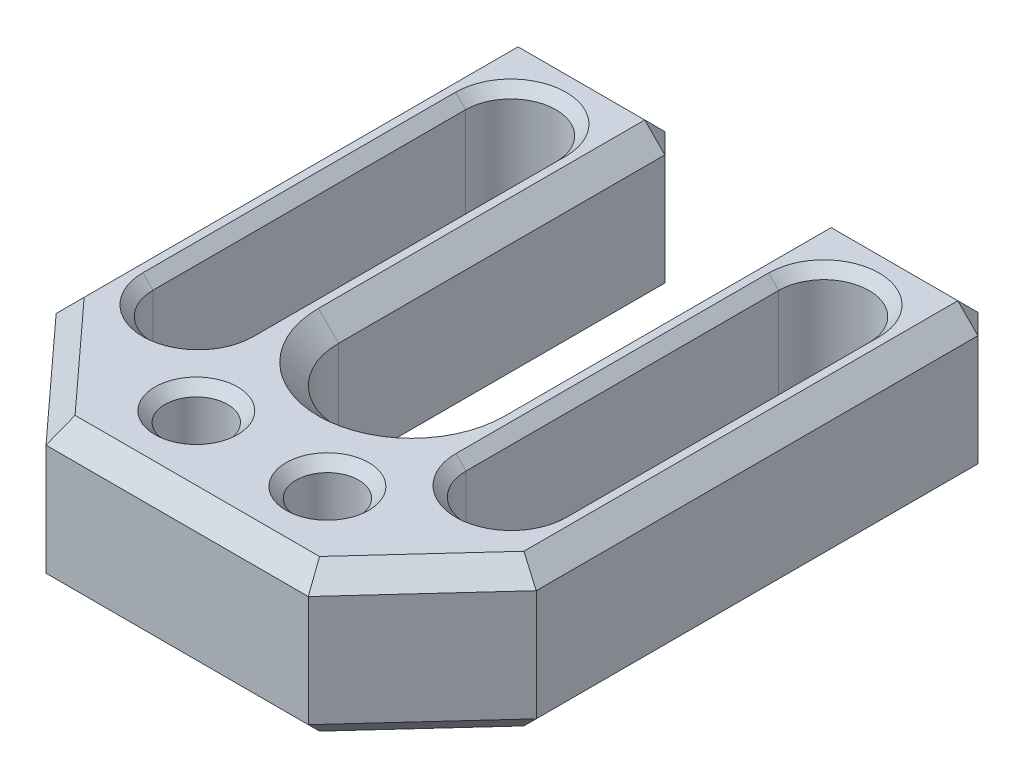
SolidWorks part; units mm, degrees
ref_plane "Front Plane" through (0, 0, 0) normal (0, 0, 1) x (1, 0, 0)
ref_plane "Top Plane" through (0, 0, 0) normal (0, 1, 0) x (1, 0, 0)
ref_plane "Right Plane" through (0, 0, 0) normal (1, 0, 0) x (0, 0, -1)
sketch "Sketch1" plane through (0, 0, 0) normal (0, 1, 0) x (1, 0, 0)
  line L0 (0, 0) -> (0, -3.62) construction
  line L1 (-3.62, 0) -> (-3.62, 17.18)
  line L2 (-3.62, 17.18) -> (-11.9, 17.18)
  line L3 (-11.9, 17.18) -> (-11.9, -5.7175)
  line L4 (-11.9, -5.7175) -> (-6.5, -11.62)
  line L5 (-6.5, -11.62) -> (0, -11.62)
  line L6 (0, -11.62) -> (0, -3.62)
  line L7 (-7.76, 12.68) -> (-7.76, -2.82) construction
  line L8 (-5.52, 12.68) -> (-5.52, -2.82)
  line L9 (-10, 12.68) -> (-10, -2.82)
  arc A0 (0, -3.62) -> (-3.62, 0) centre (0, 0) cw
  arc A1 (-5.52, 12.68) -> (-10, 12.68) centre (-7.76, 12.68) ccw
  arc A2 (-10, -2.82) -> (-5.52, -2.82) centre (-7.76, -2.82) ccw
  circle A3 centre (-3.25, -7.42) radius 1.55
  point P12 (-7.76, 4.93)
  dimension "D10" = 3.1
  dimension "D1" = 7.24
  dimension "D2" = 8
  dimension "D3" = 28.8
  dimension "D4" = 8
  dimension "D5" = 23.8
  dimension "D6" = 1.9
  dimension "D7" = 1.9
  dimension "D8" = 15.5
  dimension "D9" = 13
  dimension "D11" = 6.5
  dimension "D12" = 4.2
  dimension "D13" = 8.8
extrude "Boss-Extrude1" add sketch "Sketch1" along normal blind 2.5 contours A3 | L6 A0 L1 L2 L3 L4 L5 A3 A2 L9 A1 L8 region at (-2.7801, 0, 2.7801) region at (-3.25, 0, 7.42)
extrude "Boss-Extrude2" add sketch "Sketch1<4>" along normal blind 5 from surface starting at face at (-7.76, 2.5, -4.93)
sketch "Sketch1<4>" plane through (0, 0, 0) normal (0, 1, 0) x (1, 0, 0) same geometry as "Sketch1"
chamfer "Chamfer1" distance 1 angle 45 14 edges at (-2.5597, 0, 2.5597) (-2.5597, 7.5, 2.5597) (-11.9, 3.75, -17.18) (-3.62, 0, -8.59) (-3.25, 0, 11.62) (-9.2, 0, 8.6687) (-11.9, 0, -5.7313) (-7.76, 0, -17.18) (-3.62, 3.75, -17.18) (-3.25, 7.5, 11.62) (-9.2, 7.5, 8.6687) (-11.9, 7.5, -5.7313) (-7.76, 7.5, -17.18) (-3.62, 7.5, -8.59)
chamfer "Chamfer2" distance 0.5 angle 45 9 edges at (-7.76, 0, -14.92) (-10, 0, -4.93) (-5.52, 0, -4.93) (-7.76, 0, 5.06) (-7.76, 7.5, -14.92) (-10, 7.5, -4.93) (-5.52, 7.5, -4.93) (-7.76, 7.5, 5.06) (-3.25, 7.5, 8.97)
mirror "Mirror1" about plane through (0, 2.5, 0) normal (-1, 0, 0) of bodies 102
equation "\"D7@Sketch1\"=\"D6@Sketch1\""
